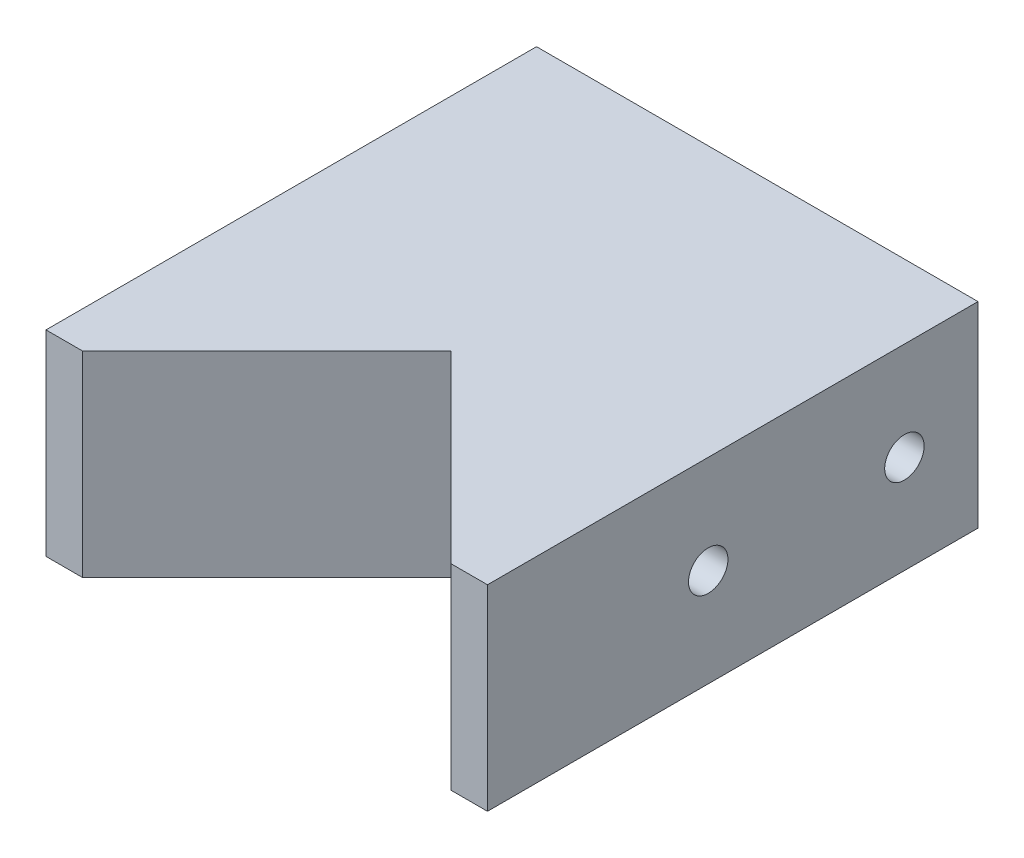
SolidWorks part; units mm, degrees
ref_plane "Front" through (0, 0, 0) normal (0, 0, 1) x (1, 0, 0)
ref_plane "Top" through (0, 0, 0) normal (0, 1, 0) x (1, 0, 0)
ref_plane "Right" through (0, 0, 0) normal (1, 0, 0) x (0, 0, -1)
sketch "Sketch1" plane through (0, 0, 0) normal (0, 0, 1) x (1, 0, 0)
  line L1 (-28.575, -12.7) -> (28.575, -12.7)
  line L2 (-28.575, -12.7) -> (-28.575, 12.7)
  line L3 (-28.575, 12.7) -> (28.575, 12.7)
  line L4 (28.575, -12.7) -> (28.575, 12.7)
  line L5 (-28.575, -12.7) -> (28.575, 12.7) construction
  line L6 (-28.575, 12.7) -> (28.575, -12.7) construction
  point P0 (0, 0)
  dimension "D1" = 57.15
  dimension "D2" = 25.4
extrude "Boss-Extrude1" add sketch "Sketch1" along normal blind 63.5
sketch "Sketch2" plane through (28.575, 0, 0) normal (1, 0, 0) x (0, 0, -1)
  line L0 (0, 0) -> (-9.525, 0) construction
  line L1 (0, -12.7) -> (0, 12.7) construction
  line L2 (-9.525, 0) -> (-34.925, 0) construction
  dimension "D1" = 9.525
  dimension "D2" = 25.4
hole_wizard "1/4-20 Tapped Hole1" positions "Sketch4" profile "Sketch3" tap size "1/4-20" standard "ANSI Inch" end condition through all
sketch "Sketch4" plane through (28.575, 0, 0) normal (1, 0, 0) x (0, 0, -1)
  point P0 (-34.925, 0)
  point P3 (-9.525, 0)
sketch "Sketch3" plane through (28.575, 0, 34.925) normal (0, 1, 0) x (0, 0, -1)
  line L0 (0, 0) -> (0, 57.15)
  line L1 (0, 57.15) -> (2.5527, 57.15)
  line L2 (2.5527, 57.15) -> (2.5527, 0)
  line L5 (2.5527, 0) -> (0, 0)
  line L11 (0, -6.35) -> (0, 107.95) construction
  dimension "Thru Tap Drill Dia." = 5.1054
  dimension "Thru Tap Drill Depth" = 57.15
cosmetic thread "Hole Thread1"
cosmetic thread "Hole Thread2"
sketch "Sketch5" plane through (0, 12.7, 0) normal (0, 1, 0) x (1, 0, 0)
  line L0 (-23.8252, -63.5) -> (0, -39.6748)
  line L1 (28.575, -63.5) -> (-28.575, -63.5) construction
  line L2 (0, -39.6748) -> (23.8252, -63.5)
  line L3 (23.8252, -63.5) -> (-23.8252, -63.5)
  line L4 (-28.575, -63.5) -> (-23.8252, -63.5) construction
  line L5 (23.8252, -63.5) -> (28.575, -63.5) construction
  dimension "D1" = 4.7498
extrude "Cut-Extrude1" cut sketch "Sketch5" against normal through all
